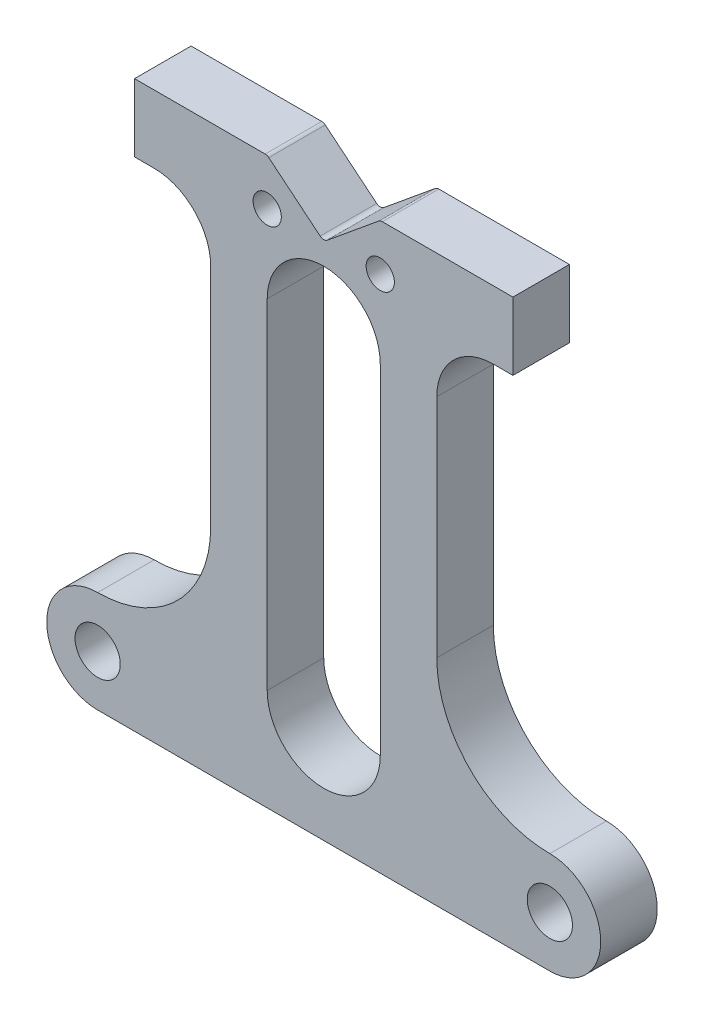
SolidWorks part; units mm, degrees
ref_plane "Front Plane" through (0, 0, 0) normal (0, 0, 1) x (1, 0, 0)
ref_plane "Top Plane" through (0, 0, 0) normal (0, 1, 0) x (1, 0, 0)
ref_plane "Right Plane" through (0, 0, 0) normal (1, 0, 0) x (0, 0, -1)
sketch "Sketch1" plane through (0, 0, 0) normal (0, 0, 1) x (1, 0, 0)
  line L0 (0, 0) -> (40, 0)
  line L5 (0, 0) -> (0, 28.65) construction
  line L6 (40, -9) -> (0, -9)
  line L7 (0, -9) -> (0, 91)
  line L8 (0, 82.7763) -> (10, 91)
  line L9 (10, 91) -> (33.47, 91)
  line L10 (33.47, 91) -> (33.47, 79)
  line L11 (33.47, 79) -> (30, 79)
  line L12 (0, 69) -> (0, 9) construction
  line L13 (20, 69) -> (20, 29)
  line L14 (10, 69) -> (10, 9)
  line L15 (-10, 69) -> (-10, 9)
  circle A0 centre (40, 0) radius 4
  circle A1 centre (40, 0) radius 9
  circle A2 centre (10, 82.7763) radius 2.5
  arc A3 (20, 69) -> (30, 79) centre (30, 69) cw
  arc A4 (20, 29) -> (40, 9) centre (40, 29) ccw
  arc A5 (10, 69) -> (-10, 69) centre (0, 69) ccw
  arc A6 (-10, 9) -> (10, 9) centre (0, 9) ccw
  point P25 (0, 39)
  point P30 (0, 0)
  point P31 (0, 0)
  dimension "D2" = 8
  dimension "D6" = 5
  dimension "D11" = 10
  dimension "D1" = 40
  dimension "D4" = 100
  dimension "D5" = 50.567
  dimension "D7" = 10
  dimension "D8" = 33.47
  dimension "D9" = 12
  dimension "D10" = 20
  dimension "D12" = 20
  dimension "D3" = 5
extrude "Boss-Extrude1" add sketch "Sketch1" along normal mid plane 10 contours A4 L13 A3 L11 L10 L9 L8 L7 L0 A1 A2 | A1 L0 L7 L6 | A1 A0 region at (17.4061, 46.8476, 0) region at (16.6759, -4.6885, 0) region at (33.816, 6.184, 0)
mirror "Mirror1" about plane through (0, 0, 5) normal (-1, 0, 0) of "Boss-Extrude1"
fillet "Fillet1" radius 1 3 edges at (-10, 91, 0) (10, 91, 0) (0, 82.7763, 0)
